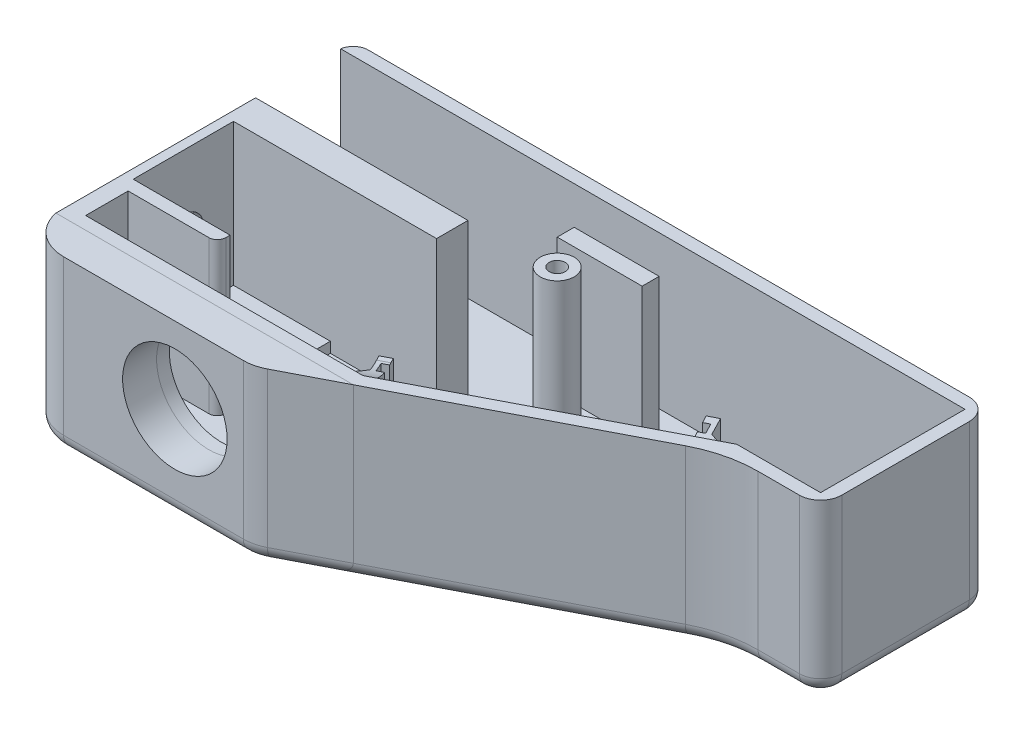
SolidWorks part; units mm, degrees
ref_plane "Front Plane" through (0, 0, 0) normal (0, 0, 1) x (1, 0, 0)
ref_plane "Top Plane" through (0, 0, 0) normal (0, 1, 0) x (1, 0, 0)
ref_plane "Right Plane" through (0, 0, 0) normal (1, 0, 0) x (0, 0, -1)
sketch "Sketch1" plane through (0, 0, 0) normal (0, 1, 0) x (1, 0, 0)
  line L5 (0, 0) -> (95.25, 0)
  line L6 (95.25, 0) -> (95.25, -25.4)
  line L7 (95.25, -25.4) -> (81.28, -25.4)
  line L8 (81.28, -25.4) -> (44.45, -44.45)
  line L9 (44.45, -44.45) -> (0, -44.45)
  line L10 (0, -44.45) -> (0, 0)
  dimension "D1" = 44.45
  dimension "D2" = 44.45
  dimension "D3" = 95.25
  dimension "D4" = 25.4
  dimension "D5" = 13.97
extrude "Boss-Extrude1" add sketch "Sketch1" along normal blind 2.54
sketch "Sketch2" plane through (0, 2.54, 0) normal (0, 1, 0) x (1, 0, 0)
  line L0 (0, 0) -> (0, -1.905)
  line L1 (0, 0) -> (0, -44.45) construction
  line L2 (0, -1.905) -> (93.345, -1.905)
  line L3 (93.345, -1.905) -> (93.345, -23.495)
  line L4 (93.345, -23.495) -> (80.8165, -23.495)
  line L5 (80.8165, -23.495) -> (43.9865, -42.545)
  line L6 (43.9865, -42.545) -> (0, -42.545)
  line L7 (0, -42.545) -> (0, -44.45)
  line L8 (0, -44.45) -> (44.45, -44.45)
  line L9 (44.45, -44.45) -> (81.28, -25.4)
  line L10 (81.28, -25.4) -> (95.25, -25.4)
  line L11 (95.25, -25.4) -> (95.25, 0)
  line L12 (95.25, 0) -> (0, 0)
  dimension "D1" = 1.905
  dimension "D2" = 1.905
  dimension "D3" = 1.905
  dimension "D4" = 1.905
  dimension "D5" = 1.905
extrude "Boss-Extrude2" add sketch "Sketch2" along normal blind 22.7965
sketch "Sketch3" plane through (0, 2.54, 0) normal (0, 1, 0) x (1, 0, 0)
  line L0 (0, -1.905) -> (0, -42.545) construction
  line L1 (0, -19.304) -> (31.75, -19.304)
  line L2 (0, -19.304) -> (0, -14.605)
  line L3 (0, -14.605) -> (31.75, -14.605)
  line L4 (31.75, -19.304) -> (31.75, -14.605)
  line L5 (0, -1.905) -> (93.345, -1.905) construction
  line L8 (0, -34.29) -> (15.875, -34.29)
  line L9 (0, -34.29) -> (0, -36.195)
  line L10 (0, -36.195) -> (15.875, -36.195)
  line L11 (15.875, -34.29) -> (15.875, -36.195)
  dimension "D1" = 19.304
  dimension "D2" = 12.7
  dimension "D3" = 31.75
  dimension "D4" = 14.986
  dimension "D5" = 1.905
  dimension "D6" = 15.875
extrude "Boss-Extrude3" add sketch "Sketch3" along normal blind 22.7965
sketch "Sketch4" plane through (0, 0, 0) normal (-1, 0, 0) x (0, 0, 1)
  line L0 (39.37, 25.3365) -> (39.37, 2.54) construction
  line L1 (36.195, 25.3365) -> (42.545, 25.3365)
  line L2 (36.195, 25.3365) -> (36.195, 2.54)
  line L3 (36.195, 2.54) -> (42.545, 2.54)
  line L4 (42.545, 25.3365) -> (42.545, 2.54)
  line L5 (36.195, 13.9383) -> (42.545, 13.9383) construction
  line L7 (40.1955, 16.3513) -> (38.5445, 16.3513)
  line L8 (40.1955, 16.3513) -> (40.1955, 11.5253)
  line L9 (40.1955, 11.5253) -> (38.5445, 11.5253)
  line L10 (38.5445, 16.3513) -> (38.5445, 11.5253)
  line L11 (40.1955, 16.3513) -> (38.5445, 11.5253) construction
  line L12 (40.1955, 11.5253) -> (38.5445, 16.3513) construction
  point P10 (39.37, 13.9383)
  dimension "D1" = 1.651
  dimension "D2" = 4.826
  dimension "D3" = 11.3983
extrude "Boss-Extrude4" add sketch "Sketch4" against normal blind 2.54
fillet "Fillet5" radius 1.27 1 edges at (15.875, 13.9383, 36.195)
sketch "Sketch6" plane through (0, 25.3365, 0) normal (0, 1, 0) x (1, 0, 0)
  line L1 (0, -44.45) -> (44.45, -44.45)
  line L2 (0, -44.45) -> (0, -49.53)
  line L3 (0, -49.53) -> (44.45, -49.53)
  line L4 (44.45, -44.45) -> (44.45, -49.53)
  dimension "D1" = 5.08
extrude "Boss-Extrude5" add sketch "Sketch6" against normal up to surface (25.3365 mm away) separate body up to face at (52.705, 0, 23.2833)
sketch "Sketch7" plane through (0, 0, 49.53) normal (0, 0, 1) x (1, 0, 0)
  line L0 (38.1, 13.9383) -> (0, 13.9382) construction
  line L3 (44.45, 25.3365) -> (44.45, 0) construction
  line L4 (0, 0) -> (44.45, 0) construction
  circle A0 centre (22.86, 13.9383) radius 7.8105
  dimension "D1" = 15.621
  dimension "D2" = 21.59
  dimension "D3" = 13.9383
extrude "Cut-Extrude1" cut sketch "Sketch7" against normal up to surface (6.985 mm away) up to face at (23.2632, 13.9383, 42.545)
sketch "Sketch9" plane through (0, 25.3365, 0) normal (0, 1, 0) x (1, 0, 0)
  line L0 (44.45, -44.45) -> (34.6287, -49.53)
  line L1 (0, -49.53) -> (44.45, -49.53) construction
  line L2 (34.6287, -49.53) -> (44.45, -49.53)
  line L3 (44.45, -49.53) -> (44.45, -44.45)
  line L4 (44.45, -44.45) -> (81.28, -25.4) construction
extrude "Cut-Extrude2" cut sketch "Sketch9" against normal through all
sketch "Sketch10" plane through (0, 2.54, 0) normal (0, 1, 0) x (1, 0, 0)
  line L0 (95.25, -25.4) -> (95.25, 0) construction
  line L1 (81.28, -25.4) -> (95.25, -25.4) construction
  circle A0 centre (44.45, -13.97) radius 2.54
  circle A2 centre (44.45, -13.97) radius 1.2065
  dimension "D1" = 5.08
  dimension "D2" = 2.413
  dimension "D3" = 50.8
  dimension "D4" = 11.43
extrude "Boss-Extrude6" add sketch "Sketch10" along normal up to surface (22.7965 mm away) up to face at (39.9659, 25.3365, 26.5734)
fillet "Fillet6" radius 19.05 1 edges at (81.28, 12.6682, 25.4)
fillet "Fillet7" radius 6.35 2 edges at (0, 12.6682, 49.53) (34.6287, 12.6682, 49.53)
fillet "Fillet8" radius 3.175 2 edges at (95.25, 12.6682, 25.4) (95.25, 12.6682, 0)
fillet "Fillet9" radius 2.2225 7 edges at (46.0375, 0, 0) (94.3201, 0, 0.9299) (95.25, 0, 12.7) (94.3201, 0, 24.4701) (88.995, 0, 25.4) (60.8065, 0, 35.9897) (81.4114, 0, 25.94)
fillet "Fillet10" radius 2.2225 4 edges at (2.2056, 0, 48.0987) (40.2255, 0, 46.6351) (34.5849, 0, 49.35) (19.6527, 0, 49.53)
fillet "Fillet11" radius 2.2225 3 edges at (0, 13.7795, 0) (0, 0.651, 0.651) (0, 0, 23.3362)
sketch "Sketch11" plane through (0, 2.54, 0) normal (0, 1, 0) x (1, 0, 0)
  line L1 (0, -19.304) -> (15.875, -19.304)
  line L2 (0, -19.304) -> (0, -34.29)
  line L3 (0, -34.29) -> (15.875, -34.29)
  line L4 (15.875, -19.304) -> (15.875, -34.29)
extrude "Boss-Extrude7" add sketch "Sketch11" along normal blind 1.5684
sketch "Sketch12" plane through (0, 0, 0) normal (-1, 0, 0) x (0, 0, 1)
  line L0 (26.797, 25.3365) -> (26.797, 4.1084) construction
  line L1 (19.304, 25.3365) -> (34.29, 25.3365)
  line L2 (19.304, 25.3365) -> (19.304, 4.1084)
  line L3 (19.304, 4.1084) -> (34.29, 4.1084)
  line L4 (34.29, 25.3365) -> (34.29, 4.1084)
  line L5 (19.304, 13.9763) -> (34.29, 13.9764) construction
  circle A0 centre (26.797, 13.9763) radius 3.048
  dimension "D1" = 6.096
  dimension "D2" = 9.8679
extrude "Boss-Extrude8" add sketch "Sketch12" against normal blind 1.397
sketch "Sketch14" plane through (0, 0, 0) normal (0, 0, -1) x (-1, 0, 0)
  line L0 (-95.25, 13.7795) -> (-0.0228, 13.9383) construction
  line L3 (-95.25, 2.2225) -> (-95.25, 25.3365) construction
  line L5 (-0.0228, 25.3365) -> (-0.0228, 2.54) construction
  circle A0 centre (-86.868, 13.7935) radius 2.5781
  dimension "D1" = 5.1562
  dimension "D2" = 8.382
extrude "Cut-Extrude3" cut sketch "Sketch14" against normal up to surface (1.905 mm away) up to face at (46.6839, 13.9383, 1.905)
sketch "Sketch15" plane through (0, 2.54, 0) normal (0, 1, 0) x (1, 0, 0)
  line L0 (31.75, -19.304) -> (31.75, -14.605) construction
  line L1 (38.1, -5.08) -> (50.8, -5.08)
  line L2 (38.1, -5.08) -> (38.1, -7.62)
  line L3 (38.1, -7.62) -> (50.8, -7.62)
  line L4 (50.8, -5.08) -> (50.8, -7.62)
  line L5 (0.0228, -1.905) -> (93.345, -1.905) construction
  point P4 (38.1, -6.35)
  dimension "D1" = 12.7
  dimension "D2" = 2.54
  dimension "D3" = 6.35
  dimension "D4" = 3.175
extrude "Boss-Extrude9" add sketch "Sketch15" along normal blind 20.32
sketch "Sketch16" plane through (0, 4.1084, 0) normal (0, 1, 0) x (1, 0, 0)
  line L0 (15.875, -19.304) -> (1.397, -19.304) construction
  line L1 (10.795, -24.384) -> (20.447, -24.384)
  line L2 (10.795, -24.384) -> (10.795, -29.337)
  line L3 (10.795, -29.337) -> (20.447, -29.337)
  line L4 (20.447, -24.384) -> (20.447, -29.337)
  line L5 (15.875, -34.29) -> (15.875, -19.304) construction
  dimension "D1" = 5.08
  dimension "D2" = 4.953
  dimension "D3" = 9.652
  dimension "D4" = 5.08
extrude "Cut-Extrude4" cut sketch "Sketch16" against normal blind 3.302
sketch "Sketch17" plane through (0, 2.54, 0) normal (0, 1, 0) x (1, 0, 0)
  line L0 (43.9865, -42.545) -> (41.4192, -37.5816)
  line L1 (41.4192, -37.5816) -> (42.8293, -36.8523)
  line L2 (42.8293, -36.8523) -> (43.4128, -37.9803)
  line L3 (43.4128, -37.9803) -> (42.5667, -38.4179)
  line L5 (80.8165, -23.495) -> (43.9865, -42.545) construction
  line L6 (45.3965, -41.8157) -> (43.9865, -42.545)
  line L8 (42.5667, -38.4179) -> (43.3836, -39.9972)
  line L9 (43.3836, -39.9972) -> (44.2296, -39.5596)
  line L10 (44.2296, -39.5596) -> (45.3965, -41.8157)
  line L11 (76.2258, -25.8695) -> (75.0588, -23.6134)
  line L12 (75.0588, -23.6134) -> (75.871, -23.1933)
  line L13 (75.871, -23.1933) -> (75.0542, -21.6141)
  line L14 (75.0542, -21.6141) -> (74.242, -22.0342)
  line L15 (74.242, -22.0342) -> (73.6585, -20.9061)
  line L16 (73.6585, -20.9061) -> (75.0686, -20.1768)
  line L17 (75.0686, -20.1768) -> (77.6358, -25.1402)
  line L18 (80.8165, -23.495) -> (43.9865, -42.545) construction
  line L19 (77.6358, -25.1402) -> (76.2258, -25.8695)
  dimension "D1" = 1.778
  dimension "D2" = 0.9144
  dimension "D3" = 4.318
  dimension "D4" = 1.27
  dimension "D5" = 1.5875
  dimension "D6" = 0.9525
  dimension "D7" = 36.576
extrude "Boss-Extrude10" add sketch "Sketch17" along normal blind 21.59
chamfer "Chamfer1" distance 2.54 angle 45 2 edges at (43.9865, 13.335, 42.545) (77.6358, 13.335, 25.1402) first distance on face at (42.7029, 13.335, 40.0633) first distance on face at (64.8122, 15.7353, 31.7731)
fillet "Fillet12" radius 10 1 edges at (44.6915, 24.13, 42.1803)
fillet "Fillet13" radius 2.54 1 edges at (44.45, 2.54, 11.43)
sketch "Sketch19" plane through (0, 0, 0) normal (-1, 0, 0) x (0, 0, 1)
  line L0 (38.5445, 11.5253) -> (40.1955, 11.5253) construction
  line L1 (38.5445, 16.3513) -> (35.2425, 16.3513)
  line L2 (38.5445, 16.3513) -> (38.5445, 11.5253)
  line L3 (38.5445, 11.5253) -> (35.2425, 11.5253)
  line L4 (35.2425, 16.3513) -> (35.2425, 11.5253)
  dimension "D1" = 3.302
extrude "Cut-Extrude5" cut sketch "Sketch19" against normal blind 1.905
sketch "Sketch22" plane through (0, 0, 0) normal (0, -1, 0) x (1, 0, 0)
  line L24 (38.2676, 28.2057) -> (39.1298, 28.8092)
  line L25 (41.0786, 21.7904) -> (41.0786, 20.7384)
  line L26 (47.6835, 18.6517) -> (47.9077, 18.6517)
  line L27 (48.2095, 18.2034) -> (48.2095, 17.5222)
  line L28 (38.7246, 20.4884) -> (38.7246, 25.1532)
  line L29 (41.0872, 24.0409) -> (41.0872, 23.4373)
  line L30 (33.8872, 28.1884) -> (37.2415, 17.0996)
  line L31 (37.0173, 16.1684) -> (35.6118, 16.1684)
  line L32 (34.7668, 16.8668) -> (32.361, 26.3518)
  line L33 (32.361, 26.3518) -> (30.1278, 16.8668)
  line L34 (29.2655, 16.177) -> (28.1101, 16.177)
  line L35 (27.2564, 16.8755) -> (25.0059, 26.4811)
  line L36 (25.0059, 26.4811) -> (22.5226, 16.8755)
  line L37 (21.6689, 16.177) -> (20.341, 16.177)
  line L38 (20.091, 17.1083) -> (23.54, 28.197)
  line L39 (24.3937, 28.8955) -> (25.6526, 28.8955)
  line L40 (26.5062, 28.1712) -> (28.7395, 18.9363)
  line L41 (28.7395, 18.9363) -> (30.9469, 28.1625)
  line L42 (31.8006, 28.8868) -> (33.0336, 28.8868)
  line L43 (19.0045, 27.6366) -> (19.0045, 26.9123)
  line L44 (18.4095, 26.5156) -> (18.0474, 26.6622)
  line L45 (13.7964, 23.7477) -> (15.8745, 23.0924)
  line L46 (10.2697, 17.3238) -> (10.2697, 18.005)
  line L47 (14.4948, 21.2213) -> (12.4599, 21.8335)
  spline S0 degree 3 poles (38.7246, 25.1532) (38.7383, 25.5846) (38.683, 26.0154) (38.5607, 26.4294) knots 0 0 0 0 1 1 1 1
  spline S1 degree 3 poles (38.5607, 26.4294) (38.4348, 26.7839) (38.279, 27.1272) (38.0951, 27.4555) knots 1 1 1 1 2 2 2 2
  spline S2 degree 3 poles (38.0951, 27.4555) (38.0325, 27.5537) (37.9968, 27.6667) (37.9916, 27.7831) knots 2 2 2 2 3 3 3 3
  spline S3 degree 3 poles (37.9916, 27.7831) (38.0101, 27.9602) (38.1128, 28.1176) (38.2676, 28.2057) knots 3 3 3 3 4 4 4 4
  spline S4 degree 3 poles (39.1298, 28.8092) (39.2414, 28.8876) (39.373, 28.9325) (39.5092, 28.9386) knots 5 5 5 5 6 6 6 6
  spline S5 degree 3 poles (39.5092, 28.9386) (39.6712, 28.9328) (39.8238, 28.8612) (39.9317, 28.7403) knots 6 6 6 6 7 7 7 7
  spline S6 degree 3 poles (39.9317, 28.7403) (40.132, 28.5421) (40.3059, 28.319) (40.4491, 28.0763) knots 7 7 7 7 8 8 8 8
  spline S7 degree 3 poles (40.4491, 28.0763) (40.5928, 27.8349) (40.7394, 27.5475) (40.8889, 27.214) knots 8 8 8 8 9 9 9 9
  spline S8 degree 3 poles (40.8889, 27.214) (41.9122, 28.4913) (43.4689, 29.2235) (45.1053, 29.1973) knots 9 9 9 9 10 10 10 10
  spline S9 degree 3 poles (45.1053, 29.1973) (46.1589, 29.255) (47.1911, 28.885) (47.9681, 28.1712) knots 10 10 10 10 11 11 11 11
  spline S10 degree 3 poles (47.9681, 28.1712) (48.6884, 27.4385) (49.0697, 26.4381) (49.02, 25.4119) knots 11 11 11 11 12 12 12 12
  spline S11 degree 3 poles (49.02, 25.4119) (49.0663, 24.2944) (48.6033, 23.2162) (47.7611, 22.4802) knots 12 12 12 12 13 13 13 13
  spline S12 degree 3 poles (47.7611, 22.4802) (46.7627, 21.694) (45.512, 21.2985) (44.2431, 21.3679) knots 13 13 13 13 14 14 14 14
  spline S13 degree 3 poles (44.2431, 21.3679) (43.7352, 21.3693) (43.2281, 21.4068) (42.7255, 21.48) knots 14 14 14 14 15 15 15 15
  spline S14 degree 3 poles (42.7255, 21.48) (42.1966, 21.5547) (41.6477, 21.6582) (41.0786, 21.7904) knots 15 15 15 15 16 16 16 16
  spline S15 degree 3 poles (41.0786, 20.7384) (40.9948, 19.914) (41.2396, 19.0898) (41.7597, 18.4448) knots 17 17 17 17 18 18 18 18
  spline S16 degree 3 poles (41.7597, 18.4448) (42.4252, 17.933) (43.2614, 17.6955) (44.0965, 17.7808) knots 18 18 18 18 19 19 19 19
  spline S17 degree 3 poles (44.0965, 17.7808) (44.6166, 17.7835) (45.1347, 17.8471) (45.64, 17.9705) knots 19 19 19 19 20 20 20 20
  spline S18 degree 3 poles (45.64, 17.9705) (46.1658, 18.0963) (46.6817, 18.2606) (47.1834, 18.462) knots 20 20 20 20 21 21 21 21
  spline S19 degree 3 poles (47.1834, 18.462) (47.3456, 18.5366) (47.5127, 18.5999) (47.6835, 18.6517) knots 21 21 21 21 22 22 22 22
  spline S20 degree 3 poles (47.9077, 18.6517) (48.1089, 18.6517) (48.2095, 18.5023) (48.2095, 18.2034) knots 23 23 23 23 24 24 24 24
  spline S21 degree 3 poles (48.2095, 17.5222) (48.2218, 17.3491) (48.186, 17.176) (48.106, 17.022) knots 25 25 25 25 26 26 26 26
  spline S22 degree 3 poles (48.106, 17.022) (47.998, 16.8895) (47.8587, 16.7858) (47.7008, 16.7202) knots 26 26 26 26 27 27 27 27
  spline S23 degree 3 poles (47.7008, 16.7202) (47.1237, 16.4438) (46.5198, 16.2271) (45.8986, 16.0735) knots 27 27 27 27 28 28 28 28
  spline S24 degree 3 poles (45.8986, 16.0735) (45.1691, 15.8862) (44.4185, 15.7935) (43.6654, 15.7976) knots 28 28 28 28 29 29 29 29
  spline S25 degree 3 poles (43.6654, 15.7976) (42.3107, 15.6776) (40.9632, 16.0957) (39.9145, 16.9617) knots 29 29 29 29 30 30 30 30
  spline S26 degree 3 poles (39.9145, 16.9617) (39.053, 17.9255) (38.623, 19.1996) (38.7246, 20.4884) knots 30 30 30 30 31 31 31 31
  spline S27 degree 3 poles (44.5449, 27.3348) (44.0392, 27.3274) (43.5382, 27.2371) (43.0618, 27.0675) knots 0 0 0 0 1 1 1 1
  spline S28 degree 3 poles (43.0618, 27.0675) (42.5366, 26.8856) (42.0693, 26.5671) (41.708, 26.1448) knots 1 1 1 1 2 2 2 2
  spline S29 degree 3 poles (41.708, 26.1448) (41.4854, 25.8966) (41.3205, 25.6021) (41.2251, 25.2826) knots 2 2 2 2 3 3 3 3
  spline S30 degree 3 poles (41.2251, 25.2826) (41.1259, 24.8763) (41.0795, 24.459) (41.0872, 24.0409) knots 3 3 3 3 4 4 4 4
  spline S31 degree 3 poles (41.0872, 23.4373) (41.5222, 23.333) (41.9626, 23.2524) (42.4064, 23.1959) knots 5 5 5 5 6 6 6 6
  spline S32 degree 3 poles (42.4064, 23.1959) (42.8526, 23.1388) (43.3018, 23.11) (43.7516, 23.1097) knots 6 6 6 6 7 7 7 7
  spline S33 degree 3 poles (43.7516, 23.1097) (44.5067, 23.053) (45.2584, 23.2569) (45.8814, 23.6874) knots 7 7 7 7 8 8 8 8
  spline S34 degree 3 poles (45.8814, 23.6874) (46.3371, 24.0894) (46.5873, 24.6754) (46.5626, 25.2826) knots 8 8 8 8 9 9 9 9
  spline S35 degree 3 poles (46.5626, 25.2826) (46.6038, 25.8393) (46.4135, 26.3883) (46.0366, 26.8002) knots 9 9 9 9 10 10 10 10
  spline S36 degree 3 poles (46.0366, 26.8002) (45.63, 27.1692) (45.0933, 27.3615) (44.5449, 27.3348) knots 10 10 10 10 11 11 11 11
  spline S37 degree 3 poles (33.0336, 28.8868) (33.2279, 28.9046) (33.4224, 28.856) (33.5854, 28.7489) knots 0 0 0 0 1 1 1 1
  spline S38 degree 3 poles (33.5854, 28.7489) (33.7381, 28.5951) (33.8429, 28.4005) (33.8872, 28.1884) knots 1 1 1 1 2 2 2 2
  spline S39 degree 3 poles (37.2415, 17.0996) (37.3065, 16.9127) (37.3499, 16.7188) (37.3708, 16.5219) knots 3 3 3 3 4 4 4 4
  spline S40 degree 3 poles (37.3708, 16.5219) (37.3966, 16.3524) (37.28, 16.1942) (37.1105, 16.1684) knots 4 4 4 4 5 5 5 5
  spline S41 degree 3 poles (37.1105, 16.1684) (37.0796, 16.1637) (37.0482, 16.1637) (37.0173, 16.1684) knots 5 5 5 5 6 6 6 6
  spline S42 degree 3 poles (35.6118, 16.1684) (35.4147, 16.1486) (35.2167, 16.1974) (35.0513, 16.3064) knots 7 7 7 7 8 8 8 8
  spline S43 degree 3 poles (35.0513, 16.3064) (34.9086, 16.4648) (34.8104, 16.6582) (34.7668, 16.8668) knots 8 8 8 8 9 9 9 9
  spline S44 degree 3 poles (30.1278, 16.8668) (30.0933, 16.6575) (29.9937, 16.4644) (29.8432, 16.315) knots 11 11 11 11 12 12 12 12
  spline S45 degree 3 poles (29.8432, 16.315) (29.6704, 16.2083) (29.4679, 16.16) (29.2655, 16.177) knots 12 12 12 12 13 13 13 13
  spline S46 degree 3 poles (28.1101, 16.177) (27.9077, 16.16) (27.7052, 16.2083) (27.5323, 16.315) knots 14 14 14 14 15 15 15 15
  spline S47 degree 3 poles (27.5323, 16.315) (27.3834, 16.4679) (27.2868, 16.6641) (27.2564, 16.8755) knots 15 15 15 15 16 16 16 16
  spline S48 degree 3 poles (22.5226, 16.8755) (22.4768, 16.6658) (22.3755, 16.4722) (22.2294, 16.315) knots 18 18 18 18 19 19 19 19
  spline S49 degree 3 poles (22.2294, 16.315) (22.064, 16.206) (21.866, 16.1573) (21.6689, 16.177) knots 19 19 19 19 20 20 20 20
  spline S50 degree 3 poles (20.341, 16.177) (20.1715, 16.1513) (20.0132, 16.2678) (19.9875, 16.4373) knots 21 21 21 21 22 22 22 22
  spline S51 degree 3 poles (19.9875, 16.4373) (19.9828, 16.4682) (19.9828, 16.4996) (19.9875, 16.5306) knots 22 22 22 22 23 23 23 23
  spline S52 degree 3 poles (19.9875, 16.5306) (19.9803, 16.6051) (19.9803, 16.6802) (19.9875, 16.7547) knots 23 23 23 23 24 24 24 24
  spline S53 degree 3 poles (19.9875, 16.7547) (20.015, 16.8745) (20.0496, 16.9926) (20.091, 17.1083) knots 24 24 24 24 25 25 25 25
  spline S54 degree 3 poles (23.54, 28.197) (23.5844, 28.4091) (23.6892, 28.6038) (23.8418, 28.7575) knots 26 26 26 26 27 27 27 27
  spline S55 degree 3 poles (23.8418, 28.7575) (24.0049, 28.8646) (24.1994, 28.9132) (24.3937, 28.8955) knots 27 27 27 27 28 28 28 28
  spline S56 degree 3 poles (25.6526, 28.8955) (25.8565, 28.9168) (26.0613, 28.8649) (26.2303, 28.7489) knots 29 29 29 29 30 30 30 30
  spline S57 degree 3 poles (26.2303, 28.7489) (26.3782, 28.5884) (26.4744, 28.3871) (26.5062, 28.1712) knots 30 30 30 30 31 31 31 31
  spline S58 degree 3 poles (30.9469, 28.1625) (30.9788, 28.3785) (31.0749, 28.5798) (31.2228, 28.7403) knots 33 33 33 33 34 34 34 34
  spline S59 degree 3 poles (31.2228, 28.7403) (31.3919, 28.8562) (31.5967, 28.9082) (31.8006, 28.8868) knots 34 34 34 34 35 35 35 35
  spline S60 degree 3 poles (14.6156, 29.2662) (15.3585, 29.2675) (16.0991, 29.1836) (16.823, 29.0162) knots 0 0 0 0 1 1 1 1
  spline S61 degree 3 poles (16.823, 29.0162) (17.3987, 28.9003) (17.9557, 28.7059) (18.4785, 28.4385) knots 1 1 1 1 2 2 2 2
  spline S62 degree 3 poles (18.4785, 28.4385) (18.8, 28.3023) (19.0077, 27.9857) (19.0045, 27.6366) knots 2 2 2 2 3 3 3 3
  spline S63 degree 3 poles (19.0045, 26.9123) (19.0045, 26.6133) (18.8953, 26.4639) (18.6768, 26.4639) knots 4 4 4 4 5 5 5 5
  spline S64 degree 3 poles (18.6768, 26.4639) (18.5854, 26.4652) (18.4949, 26.4827) (18.4095, 26.5156) knots 5 5 5 5 6 6 6 6
  spline S65 degree 3 poles (18.0474, 26.6622) (17.5413, 26.8861) (17.0121, 27.0538) (16.4694, 27.1623) knots 7 7 7 7 8 8 8 8
  spline S66 degree 3 poles (16.4694, 27.1623) (15.902, 27.2789) (15.3241, 27.3367) (14.7449, 27.3348) knots 8 8 8 8 9 9 9 9
  spline S67 degree 3 poles (14.7449, 27.3348) (14.0157, 27.378) (13.2891, 27.2135) (12.6496, 26.8605) knots 9 9 9 9 10 10 10 10
  spline S68 degree 3 poles (12.6496, 26.8605) (12.1742, 26.5781) (11.8901, 26.0594) (11.908, 25.5068) knots 10 10 10 10 11 11 11 11
  spline S69 degree 3 poles (11.908, 25.5068) (11.8981, 25.1348) (12.0379, 24.7745) (12.2961, 24.5065) knots 11 11 11 11 12 12 12 12
  spline S70 degree 3 poles (12.2961, 24.5065) (12.7313, 24.1418) (13.2447, 23.8821) (13.7964, 23.7477) knots 12 12 12 12 13 13 13 13
  spline S71 degree 3 poles (15.8745, 23.0924) (16.7495, 22.8493) (17.529, 22.3437) (18.1077, 21.6438) knots 14 14 14 14 15 15 15 15
  spline S72 degree 3 poles (18.1077, 21.6438) (18.57, 21.0495) (18.8217, 20.3186) (18.8234, 19.5657) knots 15 15 15 15 16 16 16 16
  spline S73 degree 3 poles (18.8234, 19.5657) (18.8355, 19.0093) (18.7017, 18.4593) (18.4354, 17.9705) knots 16 16 16 16 17 17 17 17
  spline S74 degree 3 poles (18.4354, 17.9705) (18.1777, 17.5108) (17.8285, 17.1087) (17.4093, 16.7892) knots 17 17 17 17 18 18 18 18
  spline S75 degree 3 poles (17.4093, 16.7892) (16.9698, 16.455) (16.4731, 16.2038) (15.9435, 16.0477) knots 18 18 18 18 19 19 19 19
  spline S76 degree 3 poles (15.9435, 16.0477) (15.3578, 15.8787) (14.7509, 15.7945) (14.1413, 15.7976) knots 19 19 19 19 20 20 20 20
  spline S77 degree 3 poles (14.1413, 15.7976) (13.8185, 15.7973) (13.4959, 15.8175) (13.1756, 15.858) knots 20 20 20 20 21 21 21 21
  spline S78 degree 3 poles (13.1756, 15.858) (12.8479, 15.8982) (12.5375, 15.9528) (12.2443, 16.0218) knots 21 21 21 21 22 22 22 22
  spline S79 degree 3 poles (12.2443, 16.0218) (11.9512, 16.0908) (11.6781, 16.1655) (11.4252, 16.246) knots 22 22 22 22 23 23 23 23
  spline S80 degree 3 poles (11.4252, 16.246) (11.217, 16.3113) (11.015, 16.395) (10.8216, 16.4961) knots 23 23 23 23 24 24 24 24
  spline S81 degree 3 poles (10.8216, 16.4961) (10.6583, 16.5841) (10.5145, 16.7044) (10.3991, 16.8496) knots 24 24 24 24 25 25 25 25
  spline S82 degree 3 poles (10.3991, 16.8496) (10.3079, 16.9905) (10.2627, 17.1562) (10.2697, 17.3238) knots 25 25 25 25 26 26 26 26
  spline S83 degree 3 poles (10.2697, 18.005) (10.2697, 18.3039) (10.379, 18.4534) (10.5974, 18.4534) knots 27 27 27 27 28 28 28 28
  spline S84 degree 3 poles (10.5974, 18.4534) (10.7907, 18.4318) (10.978, 18.3733) (11.1492, 18.281) knots 28 28 28 28 29 29 29 29
  spline S85 degree 3 poles (11.1492, 18.281) (12.0193, 17.903) (12.96, 17.7149) (13.9085, 17.7291) knots 29 29 29 29 30 30 30 30
  spline S86 degree 3 poles (13.9085, 17.7291) (14.5682, 17.6948) (15.2254, 17.8346) (15.8141, 18.1344) knots 30 30 30 30 31 31 31 31
  spline S87 degree 3 poles (15.8141, 18.1344) (16.2639, 18.3971) (16.5273, 18.8907) (16.4953, 19.4105) knots 31 31 31 31 32 32 32 32
  spline S88 degree 3 poles (16.4953, 19.4105) (16.504, 19.794) (16.3506, 20.1635) (16.0728, 20.428) knots 32 32 32 32 33 33 33 33
  spline S89 degree 3 poles (16.0728, 20.428) (15.608, 20.7998) (15.0705, 21.07) (14.4948, 21.2213) knots 33 33 33 33 34 34 34 34
  spline S90 degree 3 poles (12.4599, 21.8335) (11.5982, 22.0575) (10.8252, 22.5387) (10.2439, 23.2131) knots 35 35 35 35 36 36 36 36
  spline S91 degree 3 poles (10.2439, 23.2131) (9.788, 23.8049) (9.5504, 24.5359) (9.5713, 25.2826) knots 36 36 36 36 37 37 37 37
  spline S92 degree 3 poles (9.5713, 25.2826) (9.5637, 25.8596) (9.6938, 26.4301) (9.9507, 26.9467) knots 37 37 37 37 38 38 38 38
  spline S93 degree 3 poles (9.9507, 26.9467) (10.2018, 27.4403) (10.5579, 27.873) (10.994, 28.2143) knots 38 38 38 38 39 39 39 39
  spline S94 degree 3 poles (10.994, 28.2143) (11.4694, 28.5814) (12.011, 28.8537) (12.5892, 29.0162) knots 39 39 39 39 40 40 40 40
  spline S95 degree 3 poles (12.5892, 29.0162) (13.2491, 29.1965) (13.9316, 29.2808) (14.6156, 29.2662) knots 40 40 40 40 41 41 41 41
  spline S96 degree 3 poles (12.5892, 35.2245) (11.7959, 34.8882) (11.1234, 35.7505) (11.908, 36.3282) knots 5 5 5 5 6 6 6 6
  spline S97 degree 3 poles (28.8602, 38.5615) (23.2697, 38.5315) (17.7402, 37.3974) (12.5892, 35.2245) knots 4 4 4 4 5 5 5 5
  spline S98 degree 3 poles (50.2013, 32.8964) (43.7034, 36.6134) (36.3462, 38.5664) (28.8602, 38.5615) knots 3 3 3 3 4 4 4 4
  spline S99 degree 3 poles (50.6842, 33.5345) (51.124, 33.1378) (50.736, 32.5946) (50.2013, 32.8964) knots 2 2 2 2 3 3 3 3
  spline S100 degree 3 poles (29.3172, 41.6657) (37.2049, 41.7176) (44.8267, 38.8171) (50.6842, 33.5345) knots 1 1 1 1 2 2 2 2
  spline S101 degree 3 poles (11.908, 36.3282) (16.6246, 39.8118) (23.4711, 41.6657) (29.3172, 41.6657) knots 0 0 0 0 1 1 1 1
  spline S102 degree 3 poles (11.1837, 39.4755) (10.6146, 38.0441) (9.3385, 34.8624) (9.9421, 34.0863) knots 5 5 5 5 6 6 6 6
  spline S103 degree 3 poles (10.5974, 39.7514) (10.9854, 40.0791) (11.3562, 39.9066) (11.1837, 39.4755) knots 4 4 4 4 5 5 5 5
  spline S104 degree 3 poles (15.5727, 33.2672) (12.8738, 31.3702) (8.4417, 31.9134) (7.933, 32.5515) (7.4242, 33.1896) (8.0709, 37.6302) (10.5974, 39.7514) knots 2 2 2 2 3 3 3 4 4 4 4
  spline S105 degree 3 poles (15.452, 33.9052) (15.909, 33.957) (15.9866, 33.5603) (15.5727, 33.2672) knots 1 1 1 1 2 2 2 2
  spline S106 degree 3 poles (9.9421, 34.0863) (10.5457, 33.3103) (13.9344, 33.7242) (15.452, 33.9052) knots 0 0 0 0 1 1 1 1
sketch "Sketch25" plane through (0, 0, 0) normal (0, -1, 0) x (1, 0, 0)
  line L24 (78.5833, 10.4468) -> (78.7712, 5.4976)
  line L25 (78.7712, 5.4976) -> (80.8561, 10.4468)
  line L26 (80.8561, 10.4468) -> (82.0676, 10.4468)
  line L27 (82.0676, 10.4468) -> (82.6029, 3.9385)
  line L28 (82.6029, 3.9385) -> (81.4759, 3.9385)
  line L29 (81.4759, 3.9385) -> (81.213, 9.1977)
  line L30 (81.213, 9.1977) -> (79.1186, 4.1169)
  line L31 (79.1186, 4.1169) -> (77.8884, 4.1169)
  line L32 (77.8884, 4.1169) -> (77.7194, 9.1977)
  line L33 (77.7194, 9.1977) -> (75.5405, 3.9385)
  line L34 (75.5405, 3.9385) -> (74.3009, 3.9385)
  line L35 (74.3009, 3.9385) -> (77.3719, 10.4468)
  line L36 (77.3719, 10.4468) -> (78.5833, 10.4468)
  line L37 (74.6296, 10.4468) -> (73.6999, 5.6666)
  line L38 (73.6999, 5.6666) -> (72.5917, 5.6666)
  line L39 (72.5917, 5.6666) -> (73.5214, 10.4468)
  line L40 (73.5214, 10.4468) -> (74.6296, 10.4468)
  line L41 (69.0324, 10.4468) -> (68.5441, 7.9393)
  line L42 (70.4412, 7.3475) -> (71.0422, 10.4468)
  line L43 (71.0422, 10.4468) -> (72.1505, 10.4468)
  line L44 (72.1505, 10.4468) -> (71.2207, 5.6666)
  line L45 (71.2207, 5.6666) -> (70.3003, 5.6666)
  line L46 (70.3003, 5.6666) -> (70.3285, 6.5212)
  line L47 (67.4359, 7.9393) -> (67.9243, 10.4468)
  line L48 (67.9243, 10.4468) -> (69.0324, 10.4468)
  line L49 (63.6513, 10.4468) -> (63.6231, 9.611)
  line L50 (62.9187, 5.7042) -> (62.4867, 3.4972)
  line L51 (62.4867, 3.4972) -> (61.3785, 3.4972)
  line L52 (61.3785, 3.4972) -> (62.7309, 10.4468)
  line L53 (62.7309, 10.4468) -> (63.6513, 10.4468)
  line L54 (63.5103, 8.7844) -> (63.0596, 6.4272)
  line L55 (61.0781, 10.4468) -> (60.308, 6.493)
  line L56 (60.308, 6.493) -> (61.1251, 6.493)
  line L57 (61.1251, 6.493) -> (60.9935, 5.8168)
  line L58 (60.9935, 5.8168) -> (60.1483, 5.6948)
  line L59 (60.1483, 5.6948) -> (60.0262, 5.0561)
  line L60 (57.2276, 3.5628) -> (57.3778, 4.3141)
  line L61 (58.8992, 4.9435) -> (59.0401, 5.6666)
  line L62 (59.0401, 5.6666) -> (57.6596, 5.6666)
  line L63 (57.6596, 5.6666) -> (57.8193, 6.493)
  line L64 (57.8193, 6.493) -> (59.1998, 6.493)
  line L65 (59.1998, 6.493) -> (59.9698, 10.4468)
  line L66 (59.9698, 10.4468) -> (61.0781, 10.4468)
  line L67 (54.7859, 10.4468) -> (54.7577, 9.611)
  line L68 (53.0109, 5.9013) -> (53.8937, 10.4468)
  line L69 (53.8937, 10.4468) -> (54.7859, 10.4468)
  line L70 (54.645, 8.7844) -> (54.1943, 6.4272)
  line L71 (52.5227, 10.4468) -> (51.5929, 5.6666)
  line L72 (51.5929, 5.6666) -> (50.6725, 5.6666)
  line L73 (50.6725, 5.6666) -> (50.7007, 6.5306)
  line L74 (48.8224, 5.676) -> (49.0197, 6.6714)
  line L75 (50.8134, 7.3475) -> (51.4144, 10.4468)
  line L76 (51.4144, 10.4468) -> (52.5227, 10.4468)
  line L77 (42.9435, 10.4468) -> (42.4555, 7.9393)
  line L78 (44.3428, 7.9393) -> (44.8311, 10.4468)
  line L79 (44.8311, 10.4468) -> (45.9393, 10.4468)
  line L80 (45.9393, 10.4468) -> (45.451, 7.9393)
  line L81 (47.226, 7.3475) -> (47.827, 10.4468)
  line L82 (47.827, 10.4468) -> (48.9352, 10.4468)
  line L83 (48.9352, 10.4468) -> (48.0055, 5.6666)
  line L84 (48.0055, 5.6666) -> (47.0851, 5.6666)
  line L85 (47.0851, 5.6666) -> (47.1133, 6.5212)
  line L86 (41.3472, 7.9393) -> (41.8353, 10.4468)
  line L87 (41.8353, 10.4468) -> (42.9435, 10.4468)
  line L88 (36.6891, 10.4468) -> (35.5997, 4.8588)
  line L89 (35.5997, 4.8588) -> (37.5719, 4.8588)
  line L90 (37.5719, 4.8588) -> (37.3935, 3.9385)
  line L91 (37.3935, 3.9385) -> (32.322, 3.9385)
  line L92 (32.322, 3.9385) -> (32.5005, 4.8588)
  line L93 (32.5005, 4.8588) -> (34.4727, 4.8588)
  line L94 (34.4727, 4.8588) -> (35.5621, 10.4468)
  line L95 (35.5621, 10.4468) -> (36.6891, 10.4468)
  line L96 (30.0024, 10.4468) -> (29.9742, 9.611)
  line L97 (32.7727, 8.1741) -> (32.2844, 5.6666)
  line L98 (32.2844, 5.6666) -> (31.1762, 5.6666)
  line L99 (31.1762, 5.6666) -> (31.6645, 8.1741)
  line L100 (29.8616, 8.7844) -> (29.2604, 5.6666)
  line L101 (29.2604, 5.6666) -> (28.1522, 5.6666)
  line L102 (28.1522, 5.6666) -> (29.082, 10.4468)
  line L103 (29.082, 10.4468) -> (30.0024, 10.4468)
  line L104 (27.7391, 10.4468) -> (26.8096, 5.6666)
  line L105 (26.8096, 5.6666) -> (25.8892, 5.6666)
  line L106 (25.8892, 5.6666) -> (25.9172, 6.5306)
  line L107 (24.039, 5.676) -> (24.2362, 6.6714)
  line L108 (26.03, 7.3475) -> (26.6311, 10.4468)
  line L109 (26.6311, 10.4468) -> (27.7391, 10.4468)
  line L110 (24.1048, 10.2119) -> (22.7993, 3.4972)
  line L111 (22.7993, 3.4972) -> (21.7193, 3.4972)
  line L112 (21.7193, 3.4972) -> (22.2923, 6.4272)
  line L113 (22.4707, 7.3287) -> (22.9214, 9.686)
  line L114 (18.8834, 10.4468) -> (17.9536, 5.6666)
  line L115 (17.9536, 5.6666) -> (16.8454, 5.6666)
  line L116 (16.8454, 5.6666) -> (17.7752, 10.4468)
  line L117 (17.7752, 10.4468) -> (18.8834, 10.4468)
  line L118 (13.2861, 10.4468) -> (12.7976, 7.9393)
  line L119 (14.6947, 7.3475) -> (15.2959, 10.4468)
  line L120 (15.2959, 10.4468) -> (16.4039, 10.4468)
  line L121 (16.4039, 10.4468) -> (15.4743, 5.6666)
  line L122 (15.4743, 5.6666) -> (14.5539, 5.6666)
  line L123 (14.5539, 5.6666) -> (14.5819, 6.5212)
  line L124 (11.6895, 7.9393) -> (12.1778, 10.4468)
  line L125 (12.1778, 10.4468) -> (13.2861, 10.4468)
  line L126 (9.1845, 8.7) -> (9.7362, 8.8126)
  line L127 (7.4353, 9.3573) -> (7.1534, 9.9961)
  line L128 (9.6985, 8.0895) -> (9.1796, 7.9581)
  spline S0 degree 3 poles (72.4053, 4.6616) (72.5566, 4.8057) (72.7416, 4.8777) (72.9603, 4.8777) knots 7 7 7 7 8 8 8 8
  spline S1 degree 3 poles (73.3416, 3.8164) (73.1905, 3.6726) (73.0054, 3.6004) (72.7866, 3.6004) (72.5936, 3.6004) (72.4441, 3.6459) (72.3379, 3.7366) (72.2316, 3.8274) (72.1785, 3.9605) (72.1785, 4.1357) (72.1785, 4.3423) (72.2542, 4.5177) (72.4053, 4.6616) knots 3 3 3 3 4 4 4 5 5 5 6 6 6 7 7 7 7
  spline S2 degree 3 poles (73.4092, 4.7414) (73.5154, 4.6509) (73.5684, 4.5177) (73.5684, 4.3423) (73.5684, 4.1357) (73.4929, 3.9605) (73.3416, 3.8164) knots 1 1 1 1 2 2 2 3 3 3 3
  spline S3 degree 3 poles (72.9603, 4.8777) (73.1534, 4.8777) (73.303, 4.8324) (73.4092, 4.7414) knots 0 0 0 0 1 1 1 1
  spline S4 degree 3 poles (68.5441, 7.9393) (68.4566, 7.4759) (68.4126, 7.1409) (68.4126, 6.9345) knots 1 1 1 1 2 2 2 2
  spline S5 degree 3 poles (68.4126, 6.9345) (68.4126, 6.5651) (68.5971, 6.3804) (68.9658, 6.3804) knots 2 2 2 2 3 3 3 3
  spline S6 degree 3 poles (68.9658, 6.3804) (69.1688, 6.3804) (69.401, 6.4665) (69.6621, 6.6386) knots 3 3 3 3 4 4 4 4
  spline S7 degree 3 poles (69.6621, 6.6386) (69.9233, 6.8109) (70.1831, 7.0471) (70.4412, 7.3475) knots 4 4 4 4 5 5 5 5
  spline S8 degree 3 poles (70.3285, 6.5212) (70.0594, 6.2019) (69.7697, 5.9561) (69.4598, 5.784) knots 10 10 10 10 11 11 11 11
  spline S9 degree 3 poles (69.4598, 5.784) (69.1499, 5.6117) (68.8415, 5.5256) (68.5347, 5.5256) knots 11 11 11 11 12 12 12 12
  spline S10 degree 3 poles (68.5347, 5.5256) (68.1341, 5.5256) (67.8257, 5.6353) (67.6096, 5.8545) knots 12 12 12 12 13 13 13 13
  spline S11 degree 3 poles (67.6096, 5.8545) (67.3937, 6.0736) (67.2857, 6.3834) (67.2857, 6.784) knots 13 13 13 13 14 14 14 14
  spline S12 degree 3 poles (67.2857, 6.784) (67.2857, 7.041) (67.3359, 7.426) (67.4359, 7.9393) knots 14 14 14 14 15 15 15 15
  spline S13 degree 3 poles (63.6231, 9.611) (64.1616, 10.2622) (64.7313, 10.5876) (65.3323, 10.5876) knots 1 1 1 1 2 2 2 2
  spline S14 degree 3 poles (65.3323, 10.5876) (65.7205, 10.5876) (66.0242, 10.4483) (66.2433, 10.1697) knots 2 2 2 2 3 3 3 3
  spline S15 degree 3 poles (66.2433, 10.1697) (66.4625, 9.8911) (66.5719, 9.5015) (66.5719, 9.0005) knots 3 3 3 3 4 4 4 4
  spline S16 degree 3 poles (66.5719, 9.0005) (66.5719, 8.4182) (66.4484, 7.8627) (66.201, 7.3335) knots 4 4 4 4 5 5 5 5
  spline S17 degree 3 poles (66.201, 7.3335) (65.9538, 6.8046) (65.6126, 6.371) (65.1774, 6.0329) knots 5 5 5 5 6 6 6 6
  spline S18 degree 3 poles (65.1774, 6.0329) (64.7422, 5.6948) (64.268, 5.5256) (63.7546, 5.5256) knots 6 6 6 6 7 7 7 7
  spline S19 degree 3 poles (63.7546, 5.5256) (63.4854, 5.5256) (63.2068, 5.5853) (62.9187, 5.7042) knots 7 7 7 7 8 8 8 8
  spline S20 degree 3 poles (64.9097, 9.733) (64.7158, 9.733) (64.4997, 9.6517) (64.2617, 9.4888) knots 0 0 0 0 1 1 1 1
  spline S21 degree 3 poles (64.2617, 9.4888) (64.0239, 9.3261) (63.7734, 9.0912) (63.5103, 8.7844) knots 1 1 1 1 2 2 2 2
  spline S22 degree 3 poles (63.0596, 6.4272) (63.2349, 6.3834) (63.4291, 6.3616) (63.6419, 6.3616) knots 3 3 3 3 4 4 4 4
  spline S23 degree 3 poles (63.6419, 6.3616) (63.9487, 6.3616) (64.2415, 6.4696) (64.5199, 6.6856) knots 4 4 4 4 5 5 5 5
  spline S24 degree 3 poles (64.5199, 6.6856) (64.7986, 6.9015) (65.0287, 7.2037) (65.2102, 7.5918) knots 5 5 5 5 6 6 6 6
  spline S25 degree 3 poles (65.2102, 7.5918) (65.3919, 7.9802) (65.4825, 8.3993) (65.4825, 8.8502) knots 6 6 6 6 7 7 7 7
  spline S26 degree 3 poles (65.4825, 8.8502) (65.4825, 9.4389) (65.2916, 9.733) (64.9097, 9.733) knots 7 7 7 7 8 8 8 8
  spline S27 degree 3 poles (60.0262, 5.0561) (59.8135, 3.9291) (59.1904, 3.3658) (58.1574, 3.3658) knots 5 5 5 5 6 6 6 6
  spline S28 degree 3 poles (58.1574, 3.3658) (57.9946, 3.3658) (57.8286, 3.3843) (57.6596, 3.422) knots 6 6 6 6 7 7 7 7
  spline S29 degree 3 poles (57.6596, 3.422) (57.4905, 3.4596) (57.3466, 3.5066) (57.2276, 3.5628) knots 7 7 7 7 8 8 8 8
  spline S30 degree 3 poles (57.3778, 4.3141) (57.6223, 4.2516) (57.8483, 4.2203) (58.0561, 4.2203) knots 9 9 9 9 10 10 10 10
  spline S31 degree 3 poles (58.0561, 4.2203) (58.3127, 4.2203) (58.5053, 4.2765) (58.6335, 4.3894) knots 10 10 10 10 11 11 11 11
  spline S32 degree 3 poles (58.6335, 4.3894) (58.7618, 4.502) (58.8504, 4.6868) (58.8992, 4.9435) knots 11 11 11 11 12 12 12 12
  spline S33 degree 3 poles (54.7577, 9.611) (55.2963, 10.2622) (55.8659, 10.5876) (56.4669, 10.5876) knots 1 1 1 1 2 2 2 2
  spline S34 degree 3 poles (56.4669, 10.5876) (56.8614, 10.5876) (57.1666, 10.4468) (57.3826, 10.1651) knots 2 2 2 2 3 3 3 3
  spline S35 degree 3 poles (57.3826, 10.1651) (57.5986, 9.8833) (57.7066, 9.4857) (57.7066, 8.9723) knots 3 3 3 3 4 4 4 4
  spline S36 degree 3 poles (57.7066, 8.9723) (57.7066, 8.3899) (57.5781, 7.8376) (57.3208, 7.3147) knots 4 4 4 4 5 5 5 5
  spline S37 degree 3 poles (57.3208, 7.3147) (57.0636, 6.7921) (56.7059, 6.3631) (56.248, 6.0281) knots 5 5 5 5 6 6 6 6
  spline S38 degree 3 poles (56.248, 6.0281) (55.7901, 5.6933) (55.2914, 5.5256) (54.7519, 5.5256) knots 6 6 6 6 7 7 7 7
  spline S39 degree 3 poles (54.7519, 5.5256) (54.501, 5.5256) (54.2124, 5.5601) (53.8861, 5.629) knots 7 7 7 7 8 8 8 8
  spline S40 degree 3 poles (53.8861, 5.629) (53.5599, 5.6979) (53.2681, 5.7886) (53.0109, 5.9013) knots 8 8 8 8 9 9 9 9
  spline S41 degree 3 poles (56.0444, 9.733) (55.8504, 9.733) (55.6343, 9.6517) (55.3963, 9.4888) knots 0 0 0 0 1 1 1 1
  spline S42 degree 3 poles (55.3963, 9.4888) (55.1585, 9.3261) (54.908, 9.0912) (54.645, 8.7844) knots 1 1 1 1 2 2 2 2
  spline S43 degree 3 poles (54.1943, 6.4272) (54.3695, 6.3834) (54.5637, 6.3616) (54.7765, 6.3616) knots 3 3 3 3 4 4 4 4
  spline S44 degree 3 poles (54.7765, 6.3616) (55.0833, 6.3616) (55.3761, 6.4696) (55.6546, 6.6856) knots 4 4 4 4 5 5 5 5
  spline S45 degree 3 poles (55.6546, 6.6856) (55.9333, 6.9015) (56.1633, 7.2037) (56.3448, 7.5918) knots 5 5 5 5 6 6 6 6
  spline S46 degree 3 poles (56.3448, 7.5918) (56.5265, 7.9802) (56.6172, 8.3993) (56.6172, 8.8502) knots 6 6 6 6 7 7 7 7
  spline S47 degree 3 poles (56.6172, 8.8502) (56.6172, 9.4389) (56.4263, 9.733) (56.0444, 9.733) knots 7 7 7 7 8 8 8 8
  spline S48 degree 3 poles (50.7007, 6.5306) (50.4614, 6.2238) (50.222, 5.9968) (49.9826, 5.8496) knots 3 3 3 3 4 4 4 4
  spline S49 degree 3 poles (49.9826, 5.8496) (49.7432, 5.7027) (49.4885, 5.629) (49.2183, 5.629) knots 4 4 4 4 5 5 5 5
  spline S50 degree 3 poles (49.2183, 5.629) (49.0648, 5.629) (48.9329, 5.6447) (48.8224, 5.676) knots 5 5 5 5 6 6 6 6
  spline S51 degree 3 poles (49.0197, 6.6714) (49.216, 6.6401) (49.3723, 6.6244) (49.4887, 6.6244) knots 7 7 7 7 8 8 8 8
  spline S52 degree 3 poles (49.4887, 6.6244) (49.7279, 6.6244) (49.9611, 6.6872) (50.188, 6.8122) knots 8 8 8 8 9 9 9 9
  spline S53 degree 3 poles (50.188, 6.8122) (50.4149, 6.9375) (50.6234, 7.116) (50.8134, 7.3475) knots 9 9 9 9 10 10 10 10
  spline S54 degree 3 poles (42.4555, 7.9393) (42.3614, 7.451) (42.3142, 7.1284) (42.3142, 6.9719) knots 1 1 1 1 2 2 2 2
  spline S55 degree 3 poles (42.3142, 6.9719) (42.3142, 6.7716) (42.3544, 6.6231) (42.434, 6.5258) knots 2 2 2 2 3 3 3 3
  spline S56 degree 3 poles (42.434, 6.5258) (42.5141, 6.4289) (42.64, 6.3804) (42.8119, 6.3804) knots 3 3 3 3 4 4 4 4
  spline S57 degree 3 poles (42.8119, 6.3804) (43.2354, 6.3804) (43.7051, 6.6589) (44.2207, 7.2161) knots 4 4 4 4 5 5 5 5
  spline S58 degree 3 poles (44.2207, 7.2161) (44.2522, 7.4416) (44.2927, 7.6825) (44.3428, 7.9393) knots 5 5 5 5 6 6 6 6
  spline S59 degree 3 poles (45.451, 7.9393) (45.3634, 7.4634) (45.3195, 7.1348) (45.3195, 6.9533) knots 9 9 9 9 10 10 10 10
  spline S60 degree 3 poles (45.3195, 6.9533) (45.3195, 6.5713) (45.4761, 6.3804) (45.7892, 6.3804) knots 10 10 10 10 11 11 11 11
  spline S61 degree 3 poles (45.7892, 6.3804) (46.2253, 6.3804) (46.7041, 6.7029) (47.226, 7.3475) knots 11 11 11 11 12 12 12 12
  spline S62 degree 3 poles (47.1133, 6.5212) (46.5811, 5.8575) (46.002, 5.5256) (45.3758, 5.5256) knots 17 17 17 17 18 18 18 18
  spline S63 degree 3 poles (45.3758, 5.5256) (45.0566, 5.5256) (44.7936, 5.6135) (44.587, 5.7886) knots 18 18 18 18 19 19 19 19
  spline S64 degree 3 poles (44.587, 5.7886) (44.3804, 5.964) (44.2552, 6.2083) (44.2113, 6.5212) knots 19 19 19 19 20 20 20 20
  spline S65 degree 3 poles (44.2113, 6.5212) (43.6605, 5.8575) (43.0503, 5.5256) (42.3803, 5.5256) knots 20 20 20 20 21 21 21 21
  spline S66 degree 3 poles (42.3803, 5.5256) (41.9985, 5.5256) (41.7054, 5.6369) (41.5021, 5.859) knots 21 21 21 21 22 22 22 22
  spline S67 degree 3 poles (41.5021, 5.859) (41.2987, 6.0814) (41.1968, 6.4022) (41.1968, 6.8216) knots 22 22 22 22 23 23 23 23
  spline S68 degree 3 poles (41.1968, 6.8216) (41.1968, 7.041) (41.2471, 7.4134) (41.3472, 7.9393) knots 23 23 23 23 24 24 24 24
  spline S69 degree 3 poles (29.9742, 9.611) (30.2184, 9.9178) (30.4939, 10.1572) (30.8005, 10.3293) knots 1 1 1 1 2 2 2 2
  spline S70 degree 3 poles (30.8005, 10.3293) (31.1073, 10.5014) (31.4174, 10.5876) (31.7303, 10.5876) knots 2 2 2 2 3 3 3 3
  spline S71 degree 3 poles (31.7303, 10.5876) (32.1187, 10.5876) (32.4145, 10.4796) (32.6179, 10.2637) knots 3 3 3 3 4 4 4 4
  spline S72 degree 3 poles (32.6179, 10.2637) (32.8213, 10.0477) (32.9229, 9.7363) (32.9229, 9.3291) knots 4 4 4 4 5 5 5 5
  spline S73 degree 3 poles (32.9229, 9.3291) (32.9229, 9.0726) (32.8731, 8.6876) (32.7727, 8.1741) knots 5 5 5 5 6 6 6 6
  spline S74 degree 3 poles (31.6645, 8.1741) (31.7524, 8.6375) (31.7961, 8.9723) (31.7961, 9.1789) knots 9 9 9 9 10 10 10 10
  spline S75 degree 3 poles (31.7961, 9.1789) (31.7961, 9.3668) (31.7561, 9.5063) (31.6763, 9.5968) knots 10 10 10 10 11 11 11 11
  spline S76 degree 3 poles (31.6763, 9.5968) (31.5965, 9.6878) (31.4675, 9.733) (31.2895, 9.733) knots 11 11 11 11 12 12 12 12
  spline S77 degree 3 poles (31.2895, 9.733) (31.099, 9.733) (30.8764, 9.6484) (30.6217, 9.4794) knots 12 12 12 12 13 13 13 13
  spline S78 degree 3 poles (30.6217, 9.4794) (30.3667, 9.3103) (30.1132, 9.0788) (29.8616, 8.7844) knots 13 13 13 13 14 14 14 14
  spline S79 degree 3 poles (25.9172, 6.5306) (25.6779, 6.2238) (25.4387, 5.9968) (25.199, 5.8496) knots 3 3 3 3 4 4 4 4
  spline S80 degree 3 poles (25.199, 5.8496) (24.9598, 5.7027) (24.7051, 5.629) (24.4348, 5.629) knots 4 4 4 4 5 5 5 5
  spline S81 degree 3 poles (24.4348, 5.629) (24.2815, 5.629) (24.1494, 5.6447) (24.039, 5.676) knots 5 5 5 5 6 6 6 6
  spline S82 degree 3 poles (24.2362, 6.6714) (24.4326, 6.6401) (24.5887, 6.6244) (24.7053, 6.6244) knots 7 7 7 7 8 8 8 8
  spline S83 degree 3 poles (24.7053, 6.6244) (24.9445, 6.6244) (25.1776, 6.6872) (25.4046, 6.8122) knots 8 8 8 8 9 9 9 9
  spline S84 degree 3 poles (25.4046, 6.8122) (25.6314, 6.9375) (25.84, 7.116) (26.03, 7.3475) knots 9 9 9 9 10 10 10 10
  spline S85 degree 3 poles (22.2923, 6.4272) (21.7806, 5.8262) (21.2407, 5.5256) (20.6728, 5.5256) knots 0 0 0 0 1 1 1 1
  spline S86 degree 3 poles (20.6728, 5.5256) (20.2735, 5.5256) (19.9693, 5.6697) (19.7603, 5.9577) knots 1 1 1 1 2 2 2 2
  spline S87 degree 3 poles (19.7603, 5.9577) (19.5512, 6.2457) (19.4467, 6.6653) (19.4467, 7.2161) knots 2 2 2 2 3 3 3 3
  spline S88 degree 3 poles (19.4467, 7.2161) (19.4467, 7.8172) (19.5702, 8.3729) (19.8176, 8.883) knots 3 3 3 3 4 4 4 4
  spline S89 degree 3 poles (19.8176, 8.883) (20.0649, 9.3934) (20.4123, 9.805) (20.86, 10.1181) knots 4 4 4 4 5 5 5 5
  spline S90 degree 3 poles (20.86, 10.1181) (21.3078, 10.4312) (21.8101, 10.5876) (22.3673, 10.5876) knots 5 5 5 5 6 6 6 6
  spline S91 degree 3 poles (22.3673, 10.5876) (22.6242, 10.5876) (22.9089, 10.5533) (23.222, 10.4844) knots 6 6 6 6 7 7 7 7
  spline S92 degree 3 poles (23.222, 10.4844) (23.5352, 10.4155) (23.8293, 10.3247) (24.1048, 10.2119) knots 7 7 7 7 8 8 8 8
  spline S93 degree 3 poles (21.0968, 6.3804) (21.2837, 6.3804) (21.4972, 6.4635) (21.7368, 6.6292) knots 0 0 0 0 1 1 1 1
  spline S94 degree 3 poles (21.7368, 6.6292) (21.9769, 6.7952) (22.2214, 7.0283) (22.4707, 7.3287) knots 1 1 1 1 2 2 2 2
  spline S95 degree 3 poles (22.9214, 9.686) (22.7405, 9.73) (22.5536, 9.7518) (22.36, 9.7518) knots 3 3 3 3 4 4 4 4
  spline S96 degree 3 poles (22.36, 9.7518) (22.0235, 9.7518) (21.7178, 9.6532) (21.4434, 9.456) knots 4 4 4 4 5 5 5 5
  spline S97 degree 3 poles (21.4434, 9.456) (21.1689, 9.2587) (20.9492, 8.9801) (20.7841, 8.6202) knots 5 5 5 5 6 6 6 6
  spline S98 degree 3 poles (20.7841, 8.6202) (20.6188, 8.2603) (20.5361, 7.8485) (20.5361, 7.3852) knots 6 6 6 6 7 7 7 7
  spline S99 degree 3 poles (20.5361, 7.3852) (20.5361, 6.7154) (20.7228, 6.3804) (21.0968, 6.3804) knots 7 7 7 7 8 8 8 8
  spline S100 degree 3 poles (16.6591, 4.6616) (16.8104, 4.8057) (16.9954, 4.8777) (17.2141, 4.8777) knots 7 7 7 7 8 8 8 8
  spline S101 degree 3 poles (17.5952, 3.8164) (17.4441, 3.6726) (17.2591, 3.6004) (17.0402, 3.6004) (16.8473, 3.6004) (16.6978, 3.6459) (16.5915, 3.7366) (16.4852, 3.8274) (16.4321, 3.9605) (16.4321, 4.1357) (16.4321, 4.3423) (16.5077, 4.5177) (16.6591, 4.6616) knots 3 3 3 3 4 4 4 5 5 5 6 6 6 7 7 7 7
  spline S102 degree 3 poles (17.6628, 4.7414) (17.769, 4.6509) (17.822, 4.5177) (17.822, 4.3423) (17.822, 4.1357) (17.7465, 3.9605) (17.5952, 3.8164) knots 1 1 1 1 2 2 2 3 3 3 3
  spline S103 degree 3 poles (17.2141, 4.8777) (17.4071, 4.8777) (17.5567, 4.8324) (17.6628, 4.7414) knots 0 0 0 0 1 1 1 1
  spline S104 degree 3 poles (12.7976, 7.9393) (12.7101, 7.4759) (12.6661, 7.1409) (12.6661, 6.9345) knots 1 1 1 1 2 2 2 2
  spline S105 degree 3 poles (12.6661, 6.9345) (12.6661, 6.5651) (12.8507, 6.3804) (13.2194, 6.3804) knots 2 2 2 2 3 3 3 3
  spline S106 degree 3 poles (13.2194, 6.3804) (13.4223, 6.3804) (13.6545, 6.4665) (13.9156, 6.6386) knots 3 3 3 3 4 4 4 4
  spline S107 degree 3 poles (13.9156, 6.6386) (14.1769, 6.8109) (14.4365, 7.0471) (14.6947, 7.3475) knots 4 4 4 4 5 5 5 5
  spline S108 degree 3 poles (14.5819, 6.5212) (14.3129, 6.2019) (14.0232, 5.9561) (13.7133, 5.784) knots 10 10 10 10 11 11 11 11
  spline S109 degree 3 poles (13.7133, 5.784) (13.4035, 5.6117) (13.0952, 5.5256) (12.7884, 5.5256) knots 11 11 11 11 12 12 12 12
  spline S110 degree 3 poles (12.7884, 5.5256) (12.3878, 5.5256) (12.0792, 5.6353) (11.8632, 5.8545) knots 12 12 12 12 13 13 13 13
  spline S111 degree 3 poles (11.8632, 5.8545) (11.6471, 6.0736) (11.5391, 6.3834) (11.5391, 6.784) knots 13 13 13 13 14 14 14 14
  spline S112 degree 3 poles (11.5391, 6.784) (11.5391, 7.041) (11.5894, 7.426) (11.6895, 7.9393) knots 14 14 14 14 15 15 15 15
  spline S113 degree 3 poles (7.1534, 9.9961) (7.429, 10.1837) (7.7421, 10.3326) (8.0926, 10.4422) knots 0 0 0 0 1 1 1 1
  spline S114 degree 3 poles (8.0926, 10.4422) (8.4434, 10.5515) (8.7939, 10.6064) (9.1444, 10.6064) knots 1 1 1 1 2 2 2 2
  spline S115 degree 3 poles (9.1444, 10.6064) (9.7018, 10.6064) (10.1212, 10.4577) (10.4029, 10.1603) knots 2 2 2 2 3 3 3 3
  spline S116 degree 3 poles (10.4029, 10.1603) (10.6845, 9.8631) (10.8256, 9.4232) (10.8256, 8.8408) knots 3 3 3 3 4 4 4 4
  spline S117 degree 3 poles (10.8256, 8.8408) (10.8256, 8.2712) (10.702, 7.7344) (10.4545, 7.2301) knots 4 4 4 4 5 5 5 5
  spline S118 degree 3 poles (10.4545, 7.2301) (10.2072, 6.7263) (9.8615, 6.313) (9.4167, 5.9905) knots 5 5 5 5 6 6 6 6
  spline S119 degree 3 poles (9.4167, 5.9905) (8.9723, 5.6681) (8.484, 5.507) (7.9518, 5.507) knots 6 6 6 6 7 7 7 7
  spline S120 degree 3 poles (7.9518, 5.507) (7.5449, 5.507) (7.2256, 5.6071) (6.9938, 5.8074) knots 7 7 7 7 8 8 8 8
  spline S121 degree 3 poles (6.9938, 5.8074) (6.7622, 6.008) (6.6463, 6.2833) (6.6463, 6.6338) knots 8 8 8 8 9 9 9 9
  spline S122 degree 3 poles (6.6463, 6.6338) (6.6463, 7.1223) (6.8687, 7.5481) (7.3131, 7.9111) knots 9 9 9 9 10 10 10 10
  spline S123 degree 3 poles (7.3131, 7.9111) (7.7576, 8.2743) (8.3815, 8.5373) (9.1845, 8.7) knots 10 10 10 10 11 11 11 11
  spline S124 degree 3 poles (9.7362, 8.8126) (9.7362, 9.157) (9.6692, 9.4059) (9.5352, 9.5592) knots 12 12 12 12 13 13 13 13
  spline S125 degree 3 poles (9.5352, 9.5592) (9.4014, 9.7127) (9.182, 9.7894) (8.8779, 9.7894) knots 13 13 13 13 14 14 14 14
  spline S126 degree 3 poles (8.8779, 9.7894) (8.4397, 9.7894) (7.9588, 9.6453) (7.4353, 9.3573) knots 14 14 14 14 15 15 15 15
  spline S127 degree 3 poles (8.2286, 6.3145) (8.4421, 6.3145) (8.6496, 6.3882) (8.8512, 6.5352) knots 0 0 0 0 1 1 1 1
  spline S128 degree 3 poles (8.8512, 6.5352) (9.053, 6.6823) (9.2304, 6.892) (9.383, 7.1645) knots 1 1 1 1 2 2 2 2
  spline S129 degree 3 poles (9.383, 7.1645) (9.5359, 7.4368) (9.641, 7.7453) (9.6985, 8.0895) knots 2 2 2 2 3 3 3 3
  spline S130 degree 3 poles (9.1796, 7.9581) (8.736, 7.8455) (8.3843, 7.681) (8.125, 7.465) knots 4 4 4 4 5 5 5 5
  spline S131 degree 3 poles (8.125, 7.465) (7.8654, 7.2489) (7.7358, 7.0158) (7.7358, 6.7654) knots 5 5 5 5 6 6 6 6
  spline S132 degree 3 poles (7.7358, 6.7654) (7.7358, 6.6213) (7.7775, 6.5102) (7.8613, 6.432) knots 6 6 6 6 7 7 7 7
  spline S133 degree 3 poles (7.8613, 6.432) (7.9448, 6.3537) (8.0673, 6.3145) (8.2286, 6.3145) knots 7 7 7 7 8 8 8 8
extrude "Boss-Extrude11" add sketch "Sketch22" along normal blind 0.762
extrude "Boss-Extrude12" add sketch "Sketch25" along normal blind 0.762
chamfer "Chamfer2" distance 0.635 angle 63 1 edges at (1.905, 13.9383, 38.5445) first distance on face at (2.2225, 13.9383, 38.5445)
